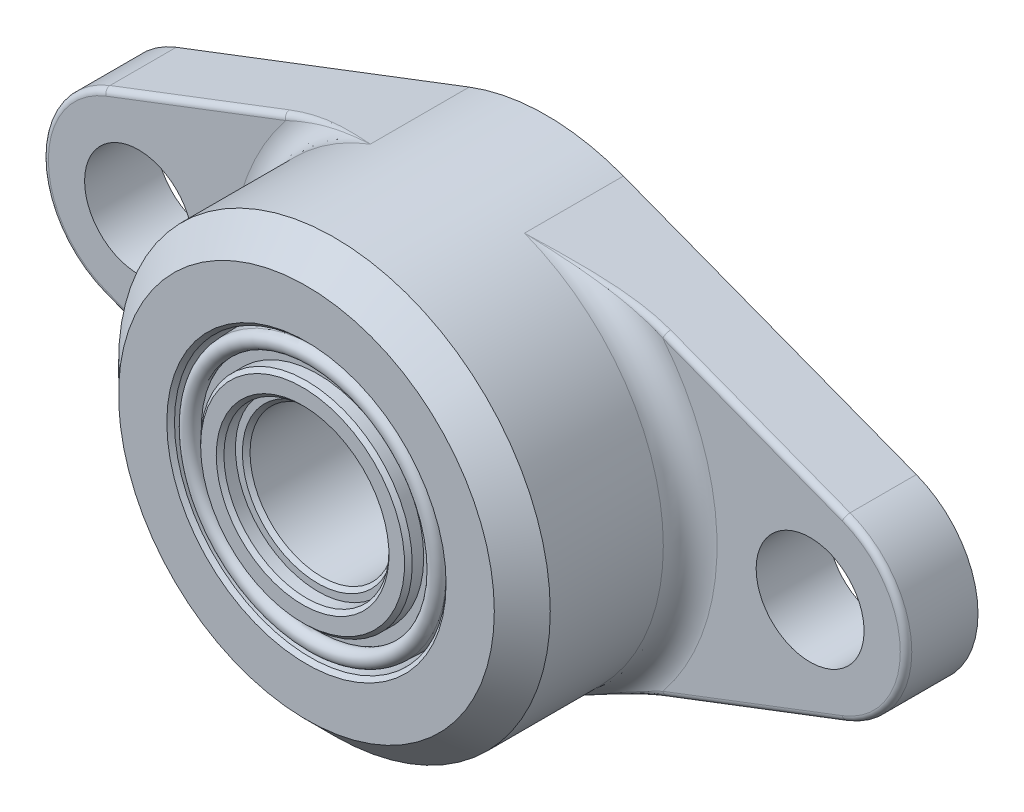
SolidWorks part; units mm, degrees
ref_plane "Front Plane" through (0, 0, 0) normal (0, 0, 1) x (1, 0, 0)
ref_plane "Top Plane" through (0, 0, 0) normal (0, 1, 0) x (1, 0, 0)
ref_plane "Right Plane" through (0, 0, 0) normal (1, 0, 0) x (0, 0, -1)
sketch "Sketch1" plane through (0, 0, 0) normal (0, 0, 1) x (1, 0, 0)
  line L0 (-22.225, 0) -> (22.225, 0) construction
  line L1 (0, 14.2875) -> (0, -14.2875) construction
  line L2 (-24.4929, 5.9312) -> (-5.1027, 13.3452)
  line L3 (5.1027, 13.3452) -> (24.4929, 5.9312)
  line L4 (24.4929, -5.9312) -> (5.1027, -13.3452)
  line L5 (-24.4929, -5.9312) -> (-5.1027, -13.3452)
  line L6 (-28.575, 0) -> (28.575, 0) construction
  line L7 (3.3586, 3.3586) -> (10.1028, 10.1028) construction
  circle A0 centre (-22.225, 0) radius 3.5719
  circle A1 centre (22.225, 0) radius 3.5719
  circle A2 centre (0, 0) radius 14.2875
  arc A3 (-24.4929, 5.9312) -> (-24.4929, -5.9312) centre (-22.225, 0) ccw
  arc A4 (24.4929, -5.9312) -> (24.4929, 5.9312) centre (22.225, 0) ccw
  circle A5 centre (0, 0) radius 4.7498
  circle A6 centre (0, 0) radius 8.9888 construction
  point P23 (6.356, 6.356)
  point P24 (0, 8.9888)
  point P25 (0, 4.7498)
  dimension "Mounting Hole" = 7.1437
  dimension "ID" = 9.4996
  dimension "D4" = 17.9776
  dimension "Mounting Center" = 44.45
  dimension "Height" = 28.575
  dimension "Length" = 57.15
  dimension "D2" = 45
  dimension "D3" = 9.5377
  dimension "D1" = 4.239
sketch "Sketch2" plane through (0, 0, 0) normal (1, 0, 0) x (0, 0, -1)
  line L0 (7.9375, 0) -> (-7.9375, 0) construction
  point P2 (3.175, 0)
  point P4 (7.9375, 0)
  dimension "Width" = 15.875
  dimension "flange thickness" = 4.7625
  dimension "Bearing Width" = 15.875
sketch "Sketch3" plane through (0, 0, 0) normal (0, 0, 1) x (1, 0, 0)
  line L0 (-24.4929, 5.9312) -> (-5.1027, 13.3452) construction
  line L1 (5.1027, 13.3452) -> (24.4929, 5.9312) construction
  line L2 (24.4929, -5.9312) -> (5.1027, -13.3452) construction
  line L3 (-24.4929, -5.9312) -> (-5.1027, -13.3452) construction
  line L4 (-24.4929, 5.9312) -> (-5.1027, 13.3452)
  line L5 (5.1027, 13.3452) -> (24.4929, 5.9312)
  line L6 (24.4929, -5.9312) -> (5.1027, -13.3452)
  line L7 (-24.4929, -5.9312) -> (-5.1027, -13.3452)
  arc A0 (-24.4929, 5.9312) -> (-24.4929, -5.9312) centre (-22.225, 0) ccw construction
  circle A1 centre (-22.225, 0) radius 3.5719 construction
  circle A2 centre (0, 0) radius 14.2875 construction
  circle A3 centre (22.225, 0) radius 3.5719 construction
  arc A4 (24.4929, -5.9312) -> (24.4929, 5.9312) centre (22.225, 0) ccw construction
  arc A5 (-24.4929, 5.9312) -> (-24.4929, -5.9312) centre (-22.225, 0) ccw
  circle A6 centre (-22.225, 0) radius 3.5719
  arc A7 (-5.1027, -13.3452) -> (5.1027, -13.3452) centre (0, 0) ccw
  circle A8 centre (22.225, 0) radius 3.5719
  arc A9 (24.4929, -5.9312) -> (24.4929, 5.9312) centre (22.225, 0) ccw
  circle A10 centre (0, 0) radius 8.9888 construction
  circle A11 centre (0, 0) radius 8.9888
  arc A12 (5.1027, 13.3452) -> (-5.1027, 13.3452) centre (0, 0) ccw
extrude "Boss-Extrude1" add sketch "Sketch3" along normal up to vertex (-3.175 mm away) from vertex at -7.9375 starting at point (0, 0, -7.9375)
sketch "Sketch4" plane through (0, 0, -3.175) normal (0, 0, 1) x (1, 0, 0)
  circle A0 centre (0, 0) radius 14.2875 construction
  circle A1 centre (0, 0) radius 8.9888 construction
  circle A2 centre (0, 0) radius 14.2875
  circle A3 centre (0, 0) radius 8.9888
extrude "Boss-Extrude2" add sketch "Sketch4" along normal up to vertex
chamfer "Chamfer1" distance 0.254 angle 45 2 edges at (8.9888, 0, 7.9375) (8.9888, 0, -7.9375)
fillet "Fillet1" radius 1.778 2 edges
fillet "Fillet2" radius 0.381 10 edges at (8.643, 11.9916, -2.6271) (28.575, 0, -3.175) (-8.643, 11.9916, -2.6271) (-28.575, 0, -3.175) (-8.643, -11.9916, -2.6271) (8.643, -11.9916, -2.6271)
chamfer "Chamfer2" distance 1.8521 angle 45 1 edges at (14.2875, 0, 7.9375)
sketch "Sketch5" plane through (0, 0, 0) normal (1, 0, 0) x (0, 0, -1)
  line L0 (-7.9375, 4.7498) -> (7.9375, 4.7498)
  line L1 (-7.9375, 4.7498) -> (-7.9375, 8.9888)
  line L2 (-7.9375, 8.9888) -> (7.9375, 8.9888)
  line L3 (7.9375, 8.9888) -> (7.9375, 4.7498)
  line L4 (-7.9375, 0) -> (7.9375, 0) construction
  dimension "D1" = 15.875
sketch "Sketch6" plane through (0, 0, 0) normal (1, 0, 0) x (0, 0, -1)
  line L0 (0, 8.9888) -> (-7.4276, 8.7294)
  line L1 (-7.1755, 7.7275) -> (-7.1755, 7.0037)
  line L2 (-7.1755, 7.0037) -> (-8.1915, 7.0037)
  line L3 (-8.1915, 7.0037) -> (-8.1915, 5.4623)
  line L4 (-7.1755, 4.7498) -> (-7.1755, 5.4623)
  line L5 (-7.1755, 5.4623) -> (-8.1915, 5.4623)
  line L6 (-7.9375, 4.7498) -> (7.9375, 4.7498) construction
  line L7 (-7.9375, 4.7498) -> (-7.9375, 8.9888) construction
  line L8 (-7.9375, 12.4354) -> (-7.9375, -12.4354) construction
  line L9 (-7.9375, 8.9888) -> (7.9375, 8.9888) construction
  line L10 (5.6515, 4.7498) -> (5.6515, 5.4623)
  line L11 (5.6515, 5.4623) -> (6.6675, 5.4623)
  line L12 (6.6675, 5.4623) -> (6.6675, 7.0037)
  line L13 (6.6675, 7.0037) -> (4.1275, 7.0037)
  line L14 (4.1275, 7.0037) -> (4.1275, 7.7275)
  line L15 (4.1275, 7.7275) -> (7.9375, 7.7275)
  line L16 (7.9375, 8.9888) -> (7.9375, 4.7498) construction
  line L17 (7.9375, 7.7275) -> (7.9375, 8.9888)
  line L18 (-7.1755, 4.7498) -> (5.6515, 4.7498)
  line L19 (0, 8.9888) -> (7.9375, 8.9888)
  line L20 (-7.9375, 0) -> (7.9375, 0) construction
  arc A0 (-7.4276, 8.7294) -> (-7.1755, 7.7275) centre (-7.4091, 8.2014) ccw
  dimension "D1" = 0.254
  dimension "D2" = 0.762
  dimension "D3" = 2
  dimension "D4" = 4.239
  dimension "D5" = 1.5414
  dimension "D6" = 10.9245
  dimension "D7" = 1.0019
  dimension "D8" = 1.27
  dimension "D9" = 2.54
revolve "Revolve1" add sketch "Sketch6" angle 360 about L20
chamfer "Chamfer3" distance 0.254 angle 45 6 edges at (5.4623, 0, -6.6675) (7.0037, 0, -6.6675) (7.0037, 0, 8.1915) (5.4623, 0, 8.1915) (4.7498, 0, 7.1755) (4.7498, 0, -5.6515)
sketch "Sketch7" plane through (0, 0, -7.9375) normal (0, 0, -1) x (-1, 0, 0)
  line L0 (-28.575, 0) -> (28.575, 0) construction
  arc A0 (-24.4929, 5.9312) -> (-24.4929, -5.9312) centre (-22.225, 0) ccw construction
  arc A1 (24.4929, -5.9312) -> (24.4929, 5.9312) centre (22.225, 0) ccw construction
equation "\"D1@Chamfer2\"=(\"Width@Sketch2\"-\"flange thickness@Sketch2\")/6"
equation "\"D1@Sketch1\"=\"D3@Sketch1\"/2.25"
equation "\"D1@Sketch5\"=\"Bearing Width@Sketch2\""
equation "\"D5@Sketch6\"=\"D4@Sketch6\"/2.75"
equation "\"D6@Sketch6\"=\"ID@Sketch1\"*1.15"
equation "\"D7@Sketch6\"=\"D5@Sketch6\"*.65"
